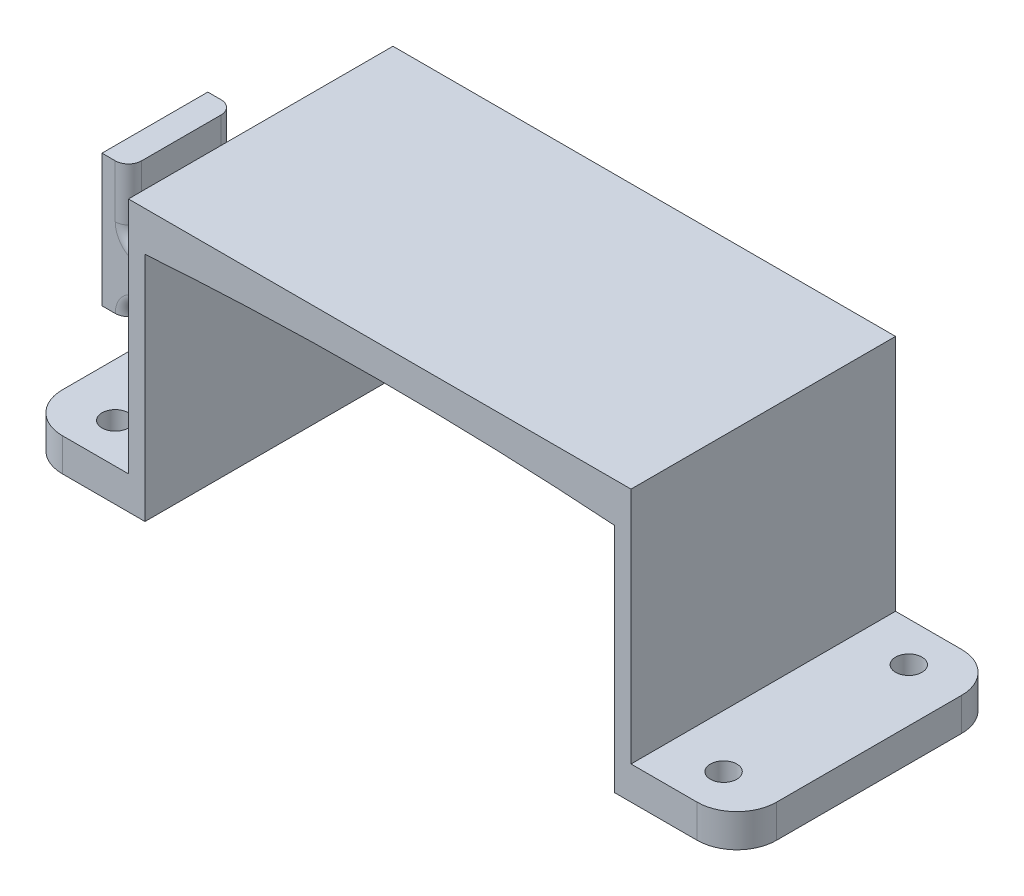
SolidWorks part; units mm, degrees
ref_plane "Front Plane" through (0, 0, 0) normal (0, 0, 1) x (1, 0, 0)
ref_plane "Top Plane" through (0, 0, 0) normal (0, 1, 0) x (1, 0, 0)
ref_plane "Right Plane" through (0, 0, 0) normal (1, 0, 0) x (0, 0, -1)
sketch "Sketch1" plane through (0, 0, 0) normal (0, 0, 1) x (1, 0, 0)
  line L0 (17, -15) -> (19, -15)
  line L1 (-19, -15) -> (-17, -15)
  line L2 (-19, -15) -> (-19, 5.5)
  line L3 (-19, 5.5) -> (19, 5.5)
  line L4 (19, -15) -> (19, 5.5)
  line L8 (-17, -15) -> (-17, 2.5)
  line L9 (-17, 2.5) -> (17, 2.5)
  line L10 (17, -15) -> (17, 2.5)
  dimension "D1" = 3
  dimension "D2" = 17.5
extrude "Boss-Extrude1" add sketch "Sketch1" along normal blind 20
sketch "Sketch2" plane through (19, 0, 0) normal (1, 0, 0) x (0, 0, -1)
  line L1 (-20, -15) -> (0, -15) construction
  line L3 (-20, -15) -> (-20, -12.5)
  line L4 (-20, -12.5) -> (0, -12.5)
  line L5 (0, -15) -> (0, -12.5)
  line L9 (-20, -15) -> (0, -15)
  point P0 (-10, -15)
  dimension "D2" = 20
extrude "Boss-Extrude2" add sketch "Sketch2" along normal blind 8
sketch "Sketch9" plane through (0, -12.5, 0) normal (0, 1, 0) x (1, 0, 0)
  line L0 (27, 0) -> (19, 0) construction
  circle A0 centre (23, -3) radius 1
  circle A1 centre (23, -17) radius 1
  dimension "D1" = 14
  dimension "D2" = 3
ref_plane "Plane1" through (0, 0, 3.25) normal (0, 0, 1) x (1, 0, 0)
ref_plane "Plane2" through (0, 0, 0) normal (1, 0, 0) x (0, 0, -1)
extrude "Corte-extrusão1" cut sketch "Sketch9" against normal through all
fillet "Filete1" radius 3 2 edges at (27, -13.75, 0) (27, -13.75, 20)
sketch "Esboço8" plane through (0, 0, 20) normal (0, 0, 1) x (1, 0, 0)
  line L0 (17, -15) -> (24, -15) construction
  line L1 (17, 2.5) -> (17.75, 2.5)
  line L2 (17, 2.5) -> (17, -15)
  line L3 (17, -15) -> (17.75, -15)
  line L4 (17.75, 2.5) -> (17.75, -15)
  line L6 (-17, 2.5) -> (-17.75, 2.5)
  line L7 (-17, 2.5) -> (-17, -15)
  line L8 (-17, -15) -> (-17.75, -15)
  line L9 (-17.75, 2.5) -> (-17.75, -15)
  dimension "D1" = 0.75
  dimension "D2" = 0.75
extrude "Corte-extrusão8" cut sketch "Esboço8" against normal through all
sketch "Esboço11" plane through (0, 0, 20) normal (0, 0, 1) x (1, 0, 0)
  line L0 (0, -9.9) -> (0, 9.9) construction
  line L1 (-17.75, 2.5) -> (17.75, 2.5)
  spline S0 degree 2 poles (-17.75, 2.5) (0, 3.7501) (17.75, 2.5) knots 0 0 0 1 1 1
extrude "Corte-extrusão9" cut sketch "Esboço11" against normal through all
mirror "Espelhar1" about plane through (0, 0, 0) normal (1, 0, 0) of "Boss-Extrude2", "Filete1", "Corte-extrusão1"
sketch "Esboço14" plane through (-19, 0, 0) normal (-1, 0, 0) x (0, 0, 1)
  line L0 (10, -12.5) -> (10, -7.5) construction
  line L1 (10, -7.5) -> (10, -5.5) construction
  line L3 (0, -12.5) -> (20, -12.5) construction
  line L4 (14, -7.5) -> (6, -7.5)
  line L5 (14, -7.5) -> (14, -3.5)
  line L6 (14, -3.5) -> (6, -3.5)
  line L7 (6, -7.5) -> (6, -3.5)
  line L8 (14, -7.5) -> (6, -3.5) construction
  line L9 (14, -3.5) -> (6, -7.5) construction
  point P4 (10, -3.8666)
  dimension "D1" = 5
  dimension "D2" = 2
  dimension "D3" = 4
  dimension "D4" = 8
extrude "Ressalto-extrusão2" add sketch "Esboço14" along normal blind 6
sketch "Esboço15" plane through (-25, 0, 0) normal (-1, 0, 0) x (0, 0, 1)
  line L0 (14, -3.5) -> (6, -7.5) construction
  line L2 (6, -8.5) -> (14, -8.5)
  line L3 (6, -8.5) -> (6, 1.5)
  line L4 (6, 1.5) -> (14, 1.5)
  line L5 (14, -8.5) -> (14, 1.5)
  line L6 (6, -8.5) -> (14, 1.5) construction
  line L7 (6, 1.5) -> (14, -8.5) construction
  point P4 (10, -5.5)
  dimension "D1" = 10
extrude "Ressalto-extrusão3" add sketch "Esboço15" along normal blind 2
fillet "Filete3" radius 1 14 edges at (-19, -5.5, 14) (-19, -5.5, 6) (-19, -7.5, 10) (-19, -3.5, 10)
